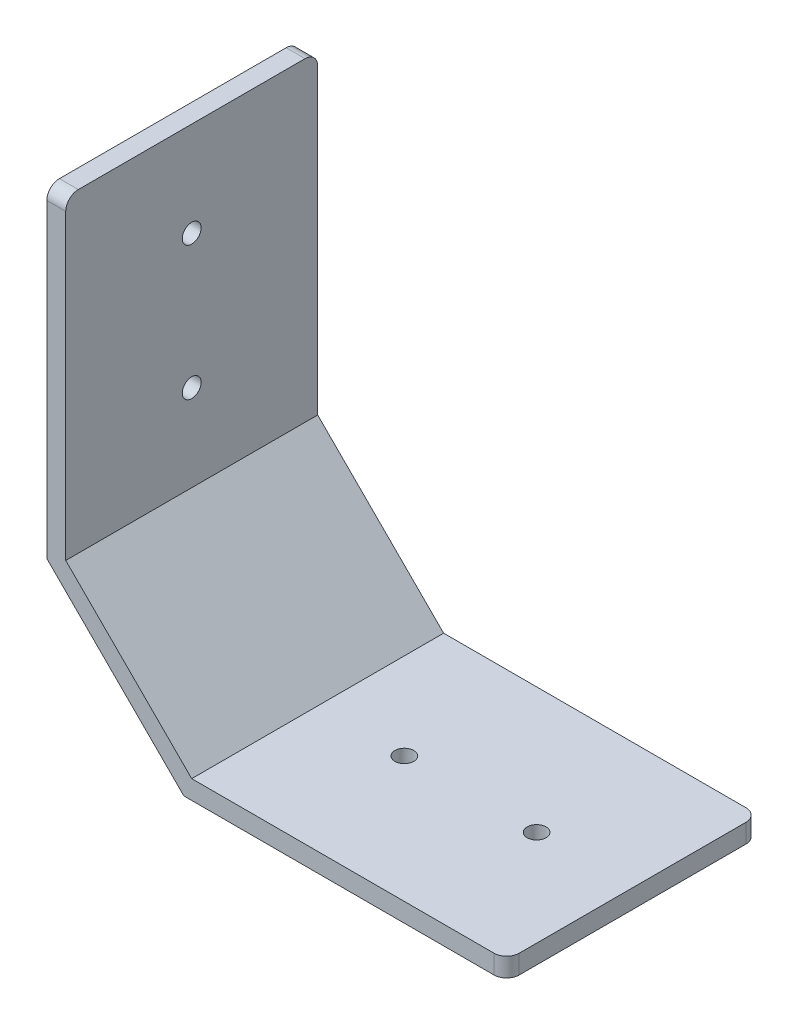
SolidWorks part; units mm, degrees
ref_plane "Plan de face" through (0, 0, 0) normal (0, 0, 1) x (1, 0, 0)
ref_plane "Plan de dessus" through (0, 0, 0) normal (0, 1, 0) x (1, 0, 0)
ref_plane "Plan de droite" through (0, 0, 0) normal (1, 0, 0) x (0, 0, -1)
sketch "Esquisse1" plane through (0, 0, 0) normal (0, 0, 1) x (1, 0, 0)
  line L0 (0, 0) -> (0, 50)
  line L1 (20, -20) -> (70, -20)
  line L2 (0, 0) -> (20, -20)
  dimension "D1" = 50
  dimension "D2" = 50
  dimension "D3" = 20
  dimension "D4" = 20
extrude "Extru.-Mince1" add sketch "Esquisse1" along normal blind 40 thin thin type one direction wall 3
fillet "Congé3" radius 2 1 edges at (-1.5, 50, 40)
fillet "Congé4" radius 2 1 edges at (-1.5, 50, 0)
fillet "Congé5" radius 2 1 edges at (70, -21.5, 40)
fillet "Congé6" radius 2 1 edges at (70, -21.5, 0)
sketch "Esquisse2" plane through (0, -23, 0) normal (0, -1, 0) x (1, 0, 0)
  line L0 (18.7574, 40) -> (68, 40) construction
  line L2 (18.7574, 40) -> (18.7574, 0) construction
  circle A0 centre (33.7574, 20) radius 1.5
  circle A1 centre (54.7574, 20) radius 1.5
  dimension "D1" = 3
  dimension "D2" = 3
  dimension "D3" = 20
  dimension "D4" = 20
  dimension "D5" = 21
  dimension "D6" = 15
extrude "Enlèv. mat.-Extru.1" cut sketch "Esquisse2" against normal blind 10
sketch "Esquisse3" plane through (-3, 0, 0) normal (-1, 0, 0) x (0, 0, 1)
  line L0 (0, 48) -> (0, -1.2426) construction
  line L1 (40, -1.2426) -> (0, -1.2426) construction
  line L2 (38, 50) -> (2, 50) construction
  circle A0 centre (20, 35) radius 1.5
  circle A1 centre (20, 13.7574) radius 1.5
  dimension "D1" = 3
  dimension "D2" = 3
  dimension "D3" = 20
  dimension "D4" = 20
  dimension "D5" = 15
  dimension "D6" = 15
extrude "Enlèv. mat.-Extru.2" cut sketch "Esquisse3" against normal blind 10
